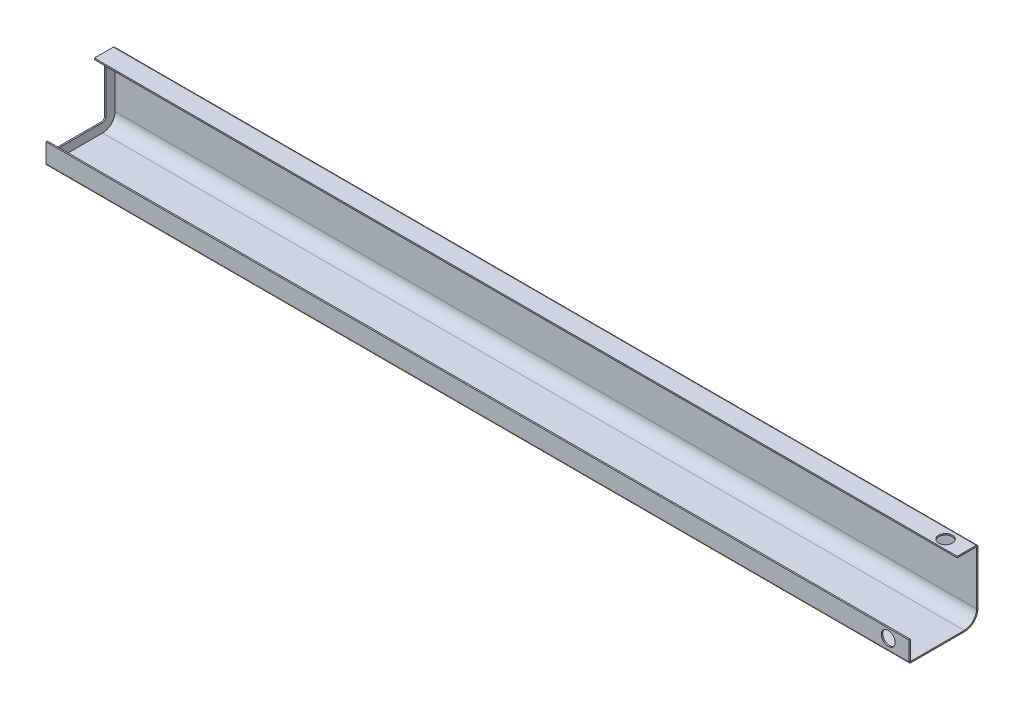
SolidWorks part; units mm, degrees
note: The reader was unsure of these and kept them because the rebuilt part matched: thickness of "基体-法兰1", "边线-法兰1", "边线-法兰2", "边线-法兰3", "钣金6", "钣金7", "钣金8", "钣金9", "钣金10", "钣金11", "钣金12"; flange length of "边线-法兰1", "边线-法兰2", "边线-法兰3".
ref_plane "前视基准面" through (0, 0, 0) normal (0, 0, 1) x (1, 0, 0)
ref_plane "上视基准面" through (0, 0, 0) normal (0, 1, 0) x (1, 0, 0)
ref_plane "右视基准面" through (0, 0, 0) normal (1, 0, 0) x (0, 0, -1)
sketch "草图2" plane through (0, 0, 0) normal (0, 0, 1) x (1, 0, 0)
  line L1 (-625, 50) -> (625, 50)
  line L2 (-625, 50) -> (-625, -50)
  line L3 (-625, -50) -> (625, -50)
  line L4 (625, 50) -> (625, -50)
  line L5 (-625, 50) -> (625, -50) construction
  line L6 (-625, -50) -> (625, 50) construction
  point P0 (0, 0)
  dimension "D1" = 1250
  dimension "D2" = 100
base flange "基体-法兰1" sketch "草图2" thickness 2 reverse thickness direction no parameters "D1"=0.7366
edge flange "边线-法兰1" sketch "草图22" flange angle 90 flange length 100 flange position material inside bend radius 18 thickness 2 relief rectangular parameters "D6"=10
bend "边线折弯4" bend radius 18 bend angle 90 parameters "D5"=1
sketch "草图22" plane through (0, -50, 0) normal (0, 1, 0) x (-1, 0, 0)
  line L0 (-625, -2) -> (625, -2) construction
  line L1 (625, 0) -> (-625, 0) construction
  line L2 (-625, 0) -> (-625, 98)
  line L3 (-625, 98) -> (625, 98)
  line L4 (625, 98) -> (625, 0)
  line L5 (625, 0) -> (-625, 0)
  dimension "D1" = 100
edge flange "边线-法兰2" sketch "草图24" flange angle 90 flange length 30 flange position material inside bend radius 0.7366 thickness 2 relief rectangular parameters "D6"=10, "D8"=1
bend "边线折弯5" bend radius 0.7366 bend angle 90 parameters "D5"=2
sketch "草图24" plane through (0, 50, 0) normal (0, -1, 0) x (1, 0, 0)
  line L1 (625, 0) -> (-625, 0) construction
  line L2 (-625, 0) -> (-625, 28)
  line L3 (-625, 28) -> (625, 28)
  line L4 (625, 28) -> (625, 0)
  line L5 (625, 0) -> (-625, 0)
edge flange "边线-法兰3" sketch "草图27" flange angle 90 flange length 30 flange position material inside bend radius 0.7366 thickness 2 relief rectangular parameters "D6"=10
sketch "草图27" plane through (0, -48, 98) normal (0, 0, -1) x (-1, 0, 0)
  line L1 (625, 0) -> (-625, 0) construction
  line L2 (-625, 0) -> (-625, 28)
  line L3 (-625, 28) -> (625, 28)
  line L4 (625, 28) -> (625, 0)
  line L5 (625, 0) -> (-625, 0)
bend "边线折弯6" bend radius 0.7366 bend angle 90 parameters "D5"=3
sketch "草图16" plane through (0, 50, 0) normal (0, 1, 0) x (1, 0, 0)
  line L0 (625, -28) -> (-625, -28) construction
  line L1 (625, -0.7366) -> (625, -28) construction
  circle A0 centre (595, -15) radius 10
  dimension "D3" = 20
  dimension "D1" = 13
  dimension "D2" = 30
extrude "切除-拉伸1" cut sketch "草图16" against normal blind 10 normal cut yes
sketch "草图17" plane through (0, 0, 98) normal (0, 0, 1) x (1, 0, 0)
  line L1 (625, -20) -> (625, -47.2634) construction
  line L2 (-625, -20) -> (625, -20) construction
  line L4 (595, 7) -> (595, -33) construction
  circle A0 centre (595, -33) radius 10
  dimension "D3" = 20
  dimension "D1" = 13
  dimension "D2" = 30
extrude "切除-拉伸2" cut sketch "草图17" against normal blind 10 normal cut yes
sketch "草图30" plane through (-625, 0, 0) normal (-1, 0, 0) x (0, 0, 1)
  line L0 (28, 50) -> (0.7366, 50) construction
  line L1 (13, 50) -> (0.7366, 50)
  line L2 (-2, 47.2634) -> (-2, -30) construction
  line L3 (-2, 47.2634) -> (-2, -30)
  line L4 (18, -50) -> (95.2634, -50) construction
  line L5 (18, -50) -> (95.2634, -50)
  line L6 (13, 50) -> (13, -30)
  line L7 (18, -35) -> (98, -35)
  line L8 (98, -47.2634) -> (98, -20) construction
  line L9 (98, -47.2634) -> (98, -35)
  arc A0 (0.7366, 50) -> (-2, 47.2634) centre (0.7366, 47.2634) ccw construction
  arc A1 (0.7366, 50) -> (-2, 47.2634) centre (0.7366, 47.2634) ccw
  arc A2 (-2, -30) -> (18, -50) centre (18, -30) ccw construction
  arc A3 (-2, -30) -> (18, -50) centre (18, -30) ccw
  arc A4 (95.2634, -50) -> (98, -47.2634) centre (95.2634, -47.2634) ccw construction
  arc A5 (95.2634, -50) -> (98, -47.2634) centre (95.2634, -47.2634) ccw
  arc A6 (13, -30) -> (18, -35) centre (18, -30) ccw
  dimension "D1" = 15
  dimension "D2" = 15
extrude "凸台-拉伸1" add sketch "草图30" against normal blind 2
sketch "折弯-线1" plane through (0, 0, 0) normal (0, 1, 0) x (1, 0, 0)
sketch "边界框1" plane through (0, 0, 0) normal (0, 1, 0) x (1, 0, 0)
sheet metal parameters "钣金6" thickness 2 parameters "D1"=0.7366, "D7"=1.5
flat pattern "平板型式6" [suppressed]
sketch "折弯-线2" plane through (0, 0, 0) normal (0, 1, 0) x (1, 0, 0)
sketch "边界框2" [suppressed] plane through (0, 0, 0) normal (0, 1, 0) x (1, 0, 0)
sheet metal parameters "钣金7" thickness 2 parameters "D1"=0.7366, "D7"=1.5
flat pattern "平板型式6" [suppressed]
sketch "折弯-线2" plane through (0, 0, 0) normal (0, 1, 0) x (1, 0, 0)
sketch "边界框2" [suppressed] plane through (0, 0, 0) normal (0, 1, 0) x (1, 0, 0)
bend of the flat pattern "展开-<边线折弯4>1"
sheet metal parameters "钣金8" thickness 2 parameters "D1"=0.7366, "D7"=1.5
flat pattern "平板型式6" [suppressed]
sketch "折弯-线2" plane through (0, 0, 0) normal (0, 1, 0) x (1, 0, 0)
sketch "边界框2" [suppressed] plane through (0, 0, 0) normal (0, 1, 0) x (1, 0, 0)
bend of the flat pattern "展开-<边线折弯4>2"
bend of the flat pattern "展开-<边线折弯5>1"
sheet metal parameters "钣金9" thickness 2 parameters "D1"=0.7366, "D7"=1.5
flat pattern "平板型式6" [suppressed]
sketch "折弯-线2" plane through (0, 0, 0) normal (0, 1, 0) x (1, 0, 0)
sketch "边界框2" [suppressed] plane through (0, 0, 0) normal (0, 1, 0) x (1, 0, 0)
bend of the flat pattern "展开-<边线折弯4>3"
bend of the flat pattern "展开-<边线折弯5>2"
bend of the flat pattern "展开-<边线折弯6>2"
sheet metal parameters "钣金10" thickness 2 parameters "D1"=0.7366, "D7"=1.5
flat pattern "平板型式6"
sketch "折弯-线2" plane through (0, 0, 0) normal (0, 0, 1) x (1, 0, 0)
  line L0 (-565, -107.0798) -> (565, -107.0798) construction
  line L1 (565, 38.02) -> (-565, 38.02) construction
  line L2 (-565, -34.5299) -> (565, -34.5299) construction
  line L3 (-565, -107.0798) -> (565, -107.0798) construction
  line L4 (565, 38.02) -> (-565, 38.02) construction
  line L5 (-565, -34.5299) -> (565, -34.5299) construction
sketch3d "边界框2" [suppressed]
  line L0 (-565, -155.0998, 0) -> (565, -155.0998, 0) construction
  line L1 (-565, 86.04, 0) -> (565, 86.04, 0) construction
  line L2 (-565, -155.0998, 0) -> (-565, 86.04, 0) construction
  line L3 (565, -155.0998, 0) -> (565, 86.04, 0) construction
bend of the flat pattern "展开-<边线折弯4>4"
bend of the flat pattern "展开-<边线折弯5>3"
bend of the flat pattern "展开-<边线折弯6>3"
sheet metal parameters "钣金11" thickness 2 parameters "D1"=0.7366, "D7"=1.5
flat pattern "平板型式6" [suppressed]
sketch "折弯-线2" plane through (0, 0, 0) normal (0, 1, 0) x (1, 0, 0)
sketch "边界框2" [suppressed] plane through (0, 0, 0) normal (0, 1, 0) x (1, 0, 0)
bend of the flat pattern "展开-<边线折弯4>2"
bend of the flat pattern "展开-<边线折弯5>1"
bend of the flat pattern "展开-<边线折弯6>1"
sheet metal parameters "钣金12" thickness 2 parameters "D1"=0.7366, "D7"=1.5
flat pattern "平板型式6"
sketch "折弯-线2" plane through (0, 0, 0) normal (0, 0, 1) x (1, 0, 0)
  line L0 (-565, -107.0798) -> (565, -107.0798) construction
  line L1 (565, 38.02) -> (-565, 38.02) construction
  line L2 (-565, -34.5299) -> (565, -34.5299) construction
  line L3 (-565, -107.0798) -> (565, -107.0798) construction
  line L4 (565, 38.02) -> (-565, 38.02) construction
  line L5 (-565, -34.5299) -> (565, -34.5299) construction
sketch3d "边界框2" [suppressed]
  line L0 (-565, -155.0998, 0) -> (565, -155.0998, 0) construction
  line L1 (-565, 86.04, 0) -> (565, 86.04, 0) construction
  line L2 (-565, -155.0998, 0) -> (-565, 86.04, 0) construction
  line L3 (565, -155.0998, 0) -> (565, 86.04, 0) construction
bend of the flat pattern "展开-<边线折弯4>4"
bend of the flat pattern "展开-<边线折弯5>3"
bend of the flat pattern "展开-<边线折弯6>3"
